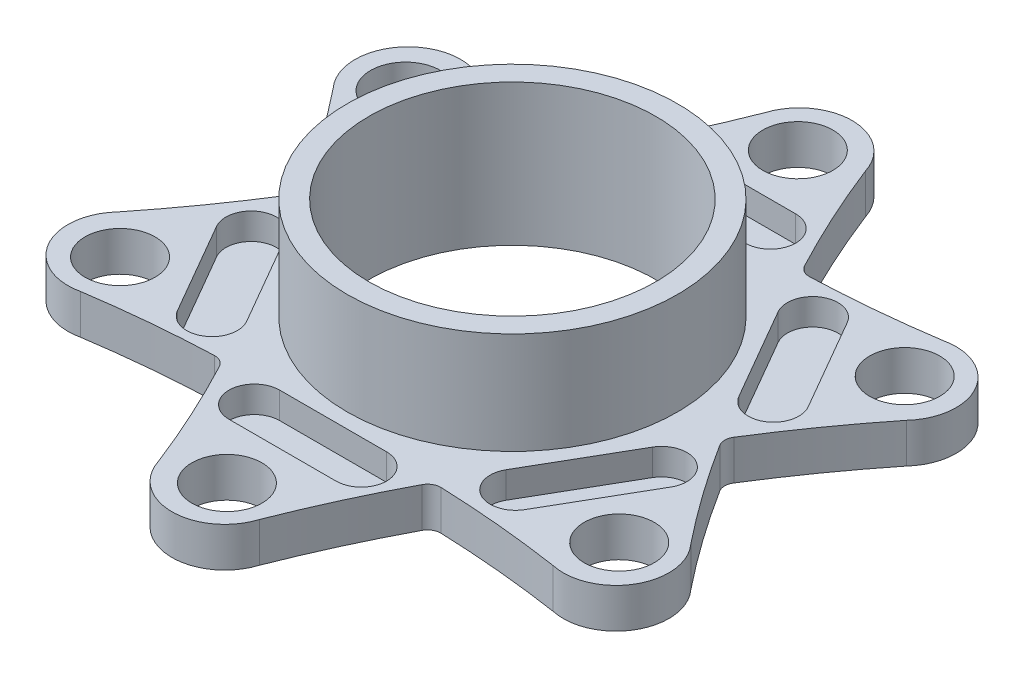
SolidWorks part; units mm, degrees
ref_plane "Front Plane" through (0, 0, 0) normal (0, 0, 1) x (1, 0, 0)
ref_plane "Top Plane" through (0, 0, 0) normal (0, 1, 0) x (1, 0, 0)
ref_plane "Right Plane" through (0, 0, 0) normal (1, 0, 0) x (0, 0, -1)
sketch "Sketch1" plane through (0, 0, 0) normal (0, 1, 0) x (1, 0, 0)
  circle A0 centre (0, 0) radius 31.75
  dimension "D1" = 63.5
extrude "CenterCircleExtrude" add sketch "Sketch1" along normal blind 19.558 contours A0
sketch "Sketch2" plane through (0, 0, 0) normal (0, -1, 0) x (1, 0, 0)
  circle A0 centre (0, 0) radius 80.01
  dimension "D1" = 160.02
extrude "BaseExpand" add sketch "Sketch2" along normal blind 7.62
sketch "Sketch3" plane through (0, 19.558, 0) normal (0, 1, 0) x (1, 0, 0)
  circle A0 centre (0, 0) radius 27.559
  dimension "D1" = 55.118
extrude "CenterCut" cut sketch "Sketch3" against normal blind 27.178 contours A0
sketch "Sketch4" plane through (0, 0, 0) normal (0, 1, 0) x (1, 0, 0)
  circle A0 centre (-0.2611, 55.1174) radius 6.731
  circle A6 centre (47.6025, 27.7848) radius 6.731
  circle A7 centre (47.8636, -27.3325) radius 6.731
  circle A8 centre (0.2611, -55.1174) radius 6.731
  circle A9 centre (-47.6025, -27.7848) radius 6.731
  circle A10 centre (-47.8636, 27.3325) radius 6.731
  point P14 (-0.2611, -0.0003)
  point P28 (0, 0)
  dimension "D1" = 13.462
  dimension "D2" = 55.118
  dimension "D4" = 6
extrude "OuterCircleCut" cut sketch "Sketch4" against normal blind 7.62
sketch "Sketch8" plane through (0, 0, 0) normal (0, 1, 0) x (1, 0, 0)
  line L4 (0, -44.5914) -> (0, -31.75) construction
  line L6 (0, -14.9479) -> (0, 14.9479) construction
  line L8 (0, 0) -> (10.16, 55.118) construction
  line L9 (10.16, 55.118) -> (-10.16, 55.118) construction
  circle A1 centre (0, 55.118) radius 10.16
  arc A6 (20.3662, 35.131) -> (9.6916, 58.1672) centre (205.1961, 134.7692) cw
  arc A7 (-20.2607, 35.327) -> (-9.6916, 58.1672) centre (-205.1961, 134.7692) ccw
  arc A8 (20.3662, 35.131) -> (46.7444, 37.6011) centre (14.018, 245.0109) ccw
  circle A9 centre (47.6361, 27.4803) radius 10.16
  arc A10 (40.51, -0.1509) -> (55.9551, 21.6476) centre (219.2142, -110.3992) cw
  arc A11 (40.51, -0.1509) -> (55.8382, -21.76) centre (219.0972, 110.2867) ccw
  circle A12 centre (47.5192, -27.5927) radius 10.16
  arc A13 (20.0268, -35.2368) -> (46.6274, -37.7135) centre (13.9011, -245.1233) cw
  arc A14 (20.0268, -35.2368) -> (8.9769, -59.316) centre (204.9622, -134.6791) ccw
  circle A15 centre (-0.2339, -55.0279) radius 10.16
  arc A16 (-20.6001, -35.0409) -> (-9.4446, -59.316) centre (-205.43, -134.6791) cw
  arc A17 (-20.6001, -35.0409) -> (-46.9782, -37.5109) centre (-14.2519, -244.9208) ccw
  circle A18 centre (-47.87, -27.3901) radius 10.16
  arc A19 (-40.7438, 0.241) -> (-56.189, -21.5575) centre (-219.448, 110.4893) cw
  arc A20 (-40.7438, 0.241) -> (-56.072, 21.8501) centre (-219.3311, -110.1966) ccw
  circle A21 centre (-47.753, 27.6828) radius 10.16
  arc A22 (-20.2607, 35.327) -> (-46.8613, 37.8036) centre (-14.135, 245.2135) cw
  point P0 (9.6916, 58.1672)
  point P14 (0, 0)
  point P27 (0, 0)
  point P63 (0, 0)
  point P72 (0, 0)
  point P74 (-0.1169, 0.0451)
  circle M12 centre (0, 0) radius 80.01
  dimension "D1" = 6
extrude "StarfishCut" cut sketch "Sketch8" against normal blind 7.62 contours A1 A9 M12 region at (-77.747, 0, 0)
sketch "Sketch14" plane through (0, 0, 0) normal (0, 1, 0) x (1, 0, 0)
  line L0 (35.0186, 8.5208) -> (24.7426, 26.3193)
  line L4 (43.446, 13.3864) -> (33.1701, 31.1849)
  line L8 (39.2323, 10.9536) -> (28.9564, 28.7521) construction
  line L11 (24.8885, -26.0665) -> (35.1645, -8.2681)
  line L14 (33.316, -30.9322) -> (43.592, -13.1337)
  line L17 (29.1023, -28.4994) -> (39.3782, -10.7009) construction
  line L24 (-10.13, -34.5874) -> (10.4219, -34.5874)
  line L27 (10.13, 39.453) -> (-10.4219, 39.453) construction
  line L28 (10.13, 34.5874) -> (-10.4219, 34.5874)
  line L29 (10.13, 44.3186) -> (-10.4219, 44.3186)
  line L30 (-10.13, -44.3186) -> (10.4219, -44.3186)
  line L33 (-10.13, -39.453) -> (10.4219, -39.453) construction
  line L36 (-35.0186, -8.5208) -> (-24.7426, -26.3193)
  line L37 (-43.446, -13.3864) -> (-33.1701, -31.1849)
  line L38 (-39.2323, -10.9536) -> (-28.9564, -28.7521) construction
  line L39 (-24.8885, 26.0665) -> (-35.1645, 8.2681)
  line L40 (-33.316, 30.9322) -> (-43.592, 13.1337)
  line L41 (-29.1023, 28.4994) -> (-39.3782, 10.7009) construction
  arc A78 (10.13, 34.5874) -> (10.13, 44.3186) centre (10.13, 39.453) ccw
  arc A79 (-10.4219, 44.3186) -> (-10.4219, 34.5874) centre (-10.4219, 39.453) ccw
  arc A84 (33.1701, 31.1849) -> (24.7426, 26.3193) centre (28.9564, 28.7521) ccw
  arc A85 (35.0186, 8.5208) -> (43.446, 13.3864) centre (39.2323, 10.9536) ccw
  arc A86 (43.592, -13.1337) -> (35.1645, -8.2681) centre (39.3782, -10.7009) ccw
  arc A87 (24.8885, -26.0665) -> (33.316, -30.9322) centre (29.1023, -28.4994) ccw
  arc A88 (10.4219, -44.3186) -> (10.4219, -34.5874) centre (10.4219, -39.453) ccw
  arc A89 (-10.13, -34.5874) -> (-10.13, -44.3186) centre (-10.13, -39.453) ccw
  arc A90 (-33.1701, -31.1849) -> (-24.7426, -26.3193) centre (-28.9564, -28.7521) ccw
  arc A91 (-35.0186, -8.5208) -> (-43.446, -13.3864) centre (-39.2323, -10.9536) ccw
  arc A92 (-43.592, 13.1337) -> (-35.1645, 8.2681) centre (-39.3782, 10.7009) ccw
  arc A93 (-24.8885, 26.0665) -> (-33.316, 30.9322) centre (-29.1023, 28.4994) ccw
  point P4 (34.0943, 19.8529)
  point P11 (34.2402, -19.6001)
  point P12 (-37.8101, 12.2891)
  point P19 (0.1459, -39.453)
  point P22 (-0.1459, 39.453)
  point P33 (-34.0943, -19.8529)
  point P34 (0, 0)
  point P41 (-34.2402, 19.6001)
  point P42 (0, 0)
  point P47 (0, 0)
  point P51 (0.0346, -0.0647)
  point P61 (0, 0)
  point P62 (37.8123, 12.2821)
  point P69 (23.3657, -32.1663)
  point P93 (0, 0)
  point P97 (0, 0)
  dimension "D1" = 6
extrude "Batman Cut" cut sketch "Sketch14" against normal blind 5.08
ref_axis "Axis1" through (0, -7.62, 0) along (0, 1, 0)
fillet "Fillet1" radius 2.54 6 edges at (20.3662, -3.81, -35.131) (-20.2607, -3.81, -35.327) (-40.7438, -3.81, -0.241) (-20.6001, -3.81, 35.0409) (20.0268, -3.81, 35.2368) (40.51, -3.81, 0.1509)
